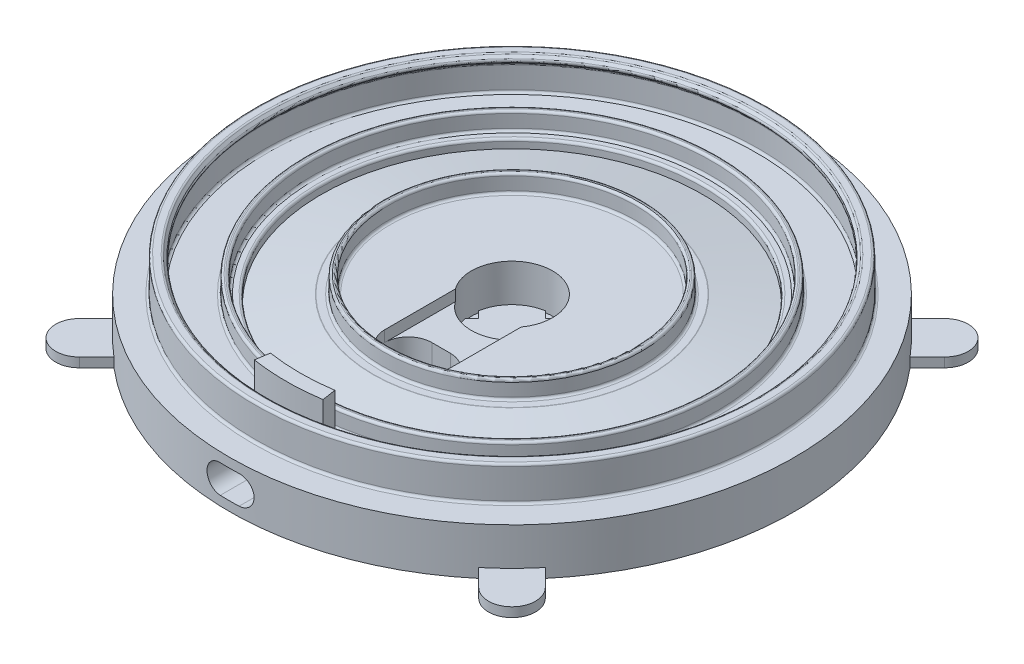
SolidWorks part; units mm, degrees
material "PLA"
ref_plane "Front Plane" through (0, 0, 0) normal (0, 0, 1) x (1, 0, 0)
ref_plane "Top Plane" through (0, 0, 0) normal (0, 1, 0) x (1, 0, 0)
ref_plane "Right Plane" through (0, 0, 0) normal (1, 0, 0) x (0, 0, -1)
sketch "Sketch1" plane through (0, 0, 0) normal (0, 1, 0) x (1, 0, 0)
  circle A0 centre (0, 0) radius 60
  circle A1 centre (0, 0) radius 40
  circle A2 centre (0, 0) radius 30
  dimension "D1" = 60
  dimension "D2" = 80
  dimension "D3" = 120
extrude "Boss-Extrude1" add sketch "Sketch1" along normal blind 10 contours A0
sketch "Sketch2" plane through (0, 0, 0) normal (0, 0, 1) x (1, 0, 0)
  line L0 (0, 10) -> (-29.5, 10)
  line L1 (60, 10) -> (-60, 10) construction
  line L2 (-29.5, 10) -> (-40.5, 8.127)
  line L3 (-40.5, 8.127) -> (-40.5, 10)
  line L4 (-40.5, 10) -> (-29.5, 10)
  line L5 (0, 10) -> (0, 0) construction
  dimension "D1" = 11
  dimension "D2" = 29.5
  dimension "D3" = 1.873
revolve "Cut-Revolve1" cut sketch "Sketch2" angle 360 about L5
sketch "Sketch3" plane through (0, 10, 0) normal (0, 1, 0) x (1, 0, 0)
  circle A0 centre (0, 0) radius 27.5
  circle A1 centre (0, 0) radius 26.25
  circle A2 centre (0, 0) radius 42.5
  circle A3 centre (0, 0) radius 43.75
  dimension "D1" = 55
  dimension "D2" = 52.5
  dimension "D3" = 85
  dimension "D4" = 87.5
extrude "Boss-Extrude2" add sketch "Sketch3" along normal blind 3.723 contours A1 | A0 | A2 | A3
fillet "Fillet1" radius 0.5 10 edges at (0, 10, 26.25) (0, 10, 27.5) (0, 10, 43.75) (0, 10, 42.5) (0, 10, 40.5) (0, 13.723, 27.5) (0, 13.723, 26.25) (0, 13.723, 43.75) (0, 13.723, 42.5) (0, 10, 29.5)
sketch "Sketch5" plane through (0, 0, 0) normal (0, 0, 1) x (1, 0, 0)
  line L0 (0, 10) -> (-52.5, 10) construction
  line L1 (60, 10) -> (-60, 10) construction
  line L2 (-52.5, 10) -> (-54.5, 10)
  line L3 (-54.5, 10) -> (-54.5, 17.323)
  line L4 (-54.5, 17.323) -> (-52.5, 17.323)
  line L5 (-52.5, 17.323) -> (-51.5, 16.323)
  line L6 (-51.5, 16.323) -> (-52.5, 15.323)
  line L7 (-52.5, 15.323) -> (-52.5, 10)
  line L8 (0, 10) -> (0, 24.5479) construction
  line L9 (0, -7.5476) -> (0, 7.5476) construction
  dimension "D1" = 52.5
  dimension "D2" = 7.323
  dimension "D3" = 1
  dimension "D4" = 1
  dimension "D5" = 2
  dimension "D6" = 2
revolve "Revolve1" add sketch "Sketch5" angle 360 about L8
fillet "Fillet2" radius 0.5 6 edges at (0, 10, -52.5) (0, 15.323, -52.5) (0, 17.323, -52.5) (0, 16.323, -51.5) (0, 10, -54.5) (0, 17.323, -54.5)
sketch "Sketch6" plane through (0, 10, 0) normal (0, 1, 0) x (1, 0, 0)
  circle A0 centre (0, 0) radius 8.625
  dimension "D1" = 17.25
extrude "Cut-Extrude1" cut sketch "Sketch6" against normal blind 8.354
sketch "Sketch9" plane through (0, 10, 0) normal (0, 1, 0) x (1, 0, 0)
  line L1 (-7, -5.0389) -> (7, -5.0389)
  line L2 (-7, -5.0389) -> (-7, -20.0389)
  line L3 (-7, -20.0389) -> (7, -20.0389)
  line L4 (7, -5.0389) -> (7, -20.0389)
  circle A0 centre (0, 0) radius 8.625 construction
  circle A1 centre (0, 0) radius 8.625 construction
  dimension "D1" = 15
  dimension "D2" = 14
extrude "Cut-Extrude2" cut sketch "Sketch9" against normal blind 2.354
sketch "Sketch10" plane through (0, 10, 0) normal (0, 1, 0) x (1, 0, 0)
  line L0 (2, -20.0389) -> (-2, -20.0389) construction
  line L1 (-7, -20.0389) -> (7, -20.0389) construction
  line L2 (2, -25.0389) -> (-2, -25.0389)
  line L3 (2, -15.0389) -> (-2, -15.0389)
  arc A0 (2, -25.0389) -> (2, -15.0389) centre (2, -20.0389) ccw
  arc A1 (-2, -15.0389) -> (-2, -25.0389) centre (-2, -20.0389) ccw
  point P4 (0, -20.0389)
  dimension "D1" = 5
extrude "Cut-Extrude3" cut sketch "Sketch10" against normal blind 10
sketch "Sketch11" plane through (0, 0, 25.0389) normal (0, 0, -1) x (-1, 0, 0)
  line L0 (-2, 5) -> (2, 5) construction
  line L1 (-2, 8) -> (2, 8)
  line L2 (-2, 2) -> (2, 2)
  line L3 (2, 0) -> (2, 10) construction
  line L4 (-2, 0) -> (-2, 10) construction
  line L5 (2, 0) -> (-2, 0) construction
  arc A0 (-2, 8) -> (-2, 2) centre (-2, 5) ccw
  arc A1 (2, 2) -> (2, 8) centre (2, 5) ccw
  point P2 (0, 5)
  dimension "D1" = 3
  dimension "D2" = 2
extrude "Cut-Extrude4" cut sketch "Sketch11" against normal blind 40 and the other way blind 2
sketch "Sketch12" plane through (0, 0, 0) normal (0, -1, 0) x (1, 0, 0)
  line L0 (-45.9619, -45.9619) -> (45.9619, 45.9619) construction
  line L1 (-49.4975, -42.4264) -> (42.4264, 49.4975)
  line L2 (-42.4264, -49.4975) -> (49.4975, 42.4264)
  line L3 (9.5276, 0) -> (-9.5276, 0) construction
  line L4 (45.9619, -45.9619) -> (-45.9619, 45.9619) construction
  line L5 (42.4264, -49.4975) -> (-49.4975, 42.4264)
  line L6 (49.4975, -42.4264) -> (-42.4264, 49.4975)
  line L7 (0, -9.5276) -> (0, 9.5276) construction
  arc A0 (-49.4975, -42.4264) -> (-42.4264, -49.4975) centre (-45.9619, -45.9619) ccw
  arc A1 (49.4975, 42.4264) -> (42.4264, 49.4975) centre (45.9619, 45.9619) ccw
  circle A2 centre (0, 0) radius 60 construction
  arc A3 (42.4264, -49.4975) -> (49.4975, -42.4264) centre (45.9619, -45.9619) ccw
  arc A4 (-42.4264, 49.4975) -> (-49.4975, 42.4264) centre (-45.9619, 45.9619) ccw
  point P2 (0, 0)
  point P14 (0, 0)
  dimension "D2" = 5
  dimension "D4" = 5
  dimension "D1" = 65
  dimension "D3" = 45
  dimension "D5" = 65
  dimension "D6" = 45
extrude "Boss-Extrude3" add sketch "Sketch12" against normal blind 2 contours L6 A4 L5 A3 | L2 A1 L1 A0
sketch "Sketch13" plane through (0, 10, 0) normal (0, 1, 0) x (1, 0, 0)
  line L0 (-7.3019, -47.4414) -> (-6.8456, -44.4763)
  line L1 (-6.8456, -44.4763) -> (0, 0) construction
  line L2 (0, 0) -> (6.8456, -44.4763) construction
  line L3 (6.8456, -44.4763) -> (7.3019, -47.4414)
  line L4 (0, -9.5276) -> (0, 9.5276) construction
  arc A0 (-6.8456, -44.4763) -> (6.8456, -44.4763) centre (0, 0) ccw
  arc A1 (-7.3019, -47.4414) -> (7.3019, -47.4414) centre (0, 0) ccw
  point P6 (0, -48)
  dimension "D1" = 45
  dimension "D2" = 48
  dimension "D3" = 17.5
  dimension "D4" = 17.5
extrude "Boss-Extrude4" add sketch "Sketch13" along normal blind 8
